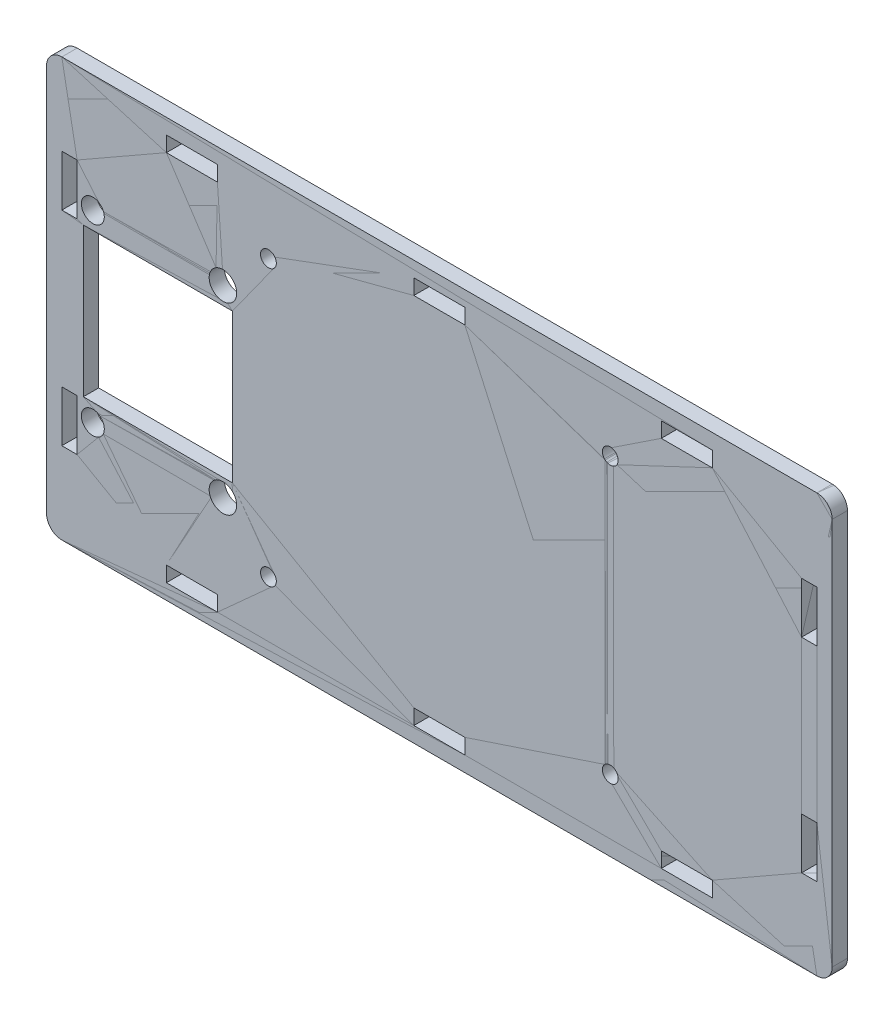
SolidWorks part; units mm, degrees
ref_plane "前视基准面" through (0, 0, 0) normal (0, 0, 1) x (1, 0, 0)
ref_plane "上视基准面" through (0, 0, 0) normal (0, 1, 0) x (1, 0, 0)
ref_plane "右视基准面" through (0, 0, 0) normal (1, 0, 0) x (0, 0, -1)
sketch "草图1" plane through (0, 0, 0) normal (0, 0, 1) x (1, 0, 0)
  line L0 (0, -9.5012) -> (46.4632, -9.5012) construction
  line L1 (-74, 31.4988) -> (74, 31.4988)
  line L2 (-77, 28.4988) -> (-77, -47.5012)
  line L3 (-74, -50.5012) -> (74, -50.5012)
  line L4 (77, 28.4988) -> (77, -47.5012)
  line L5 (-77, 31.4988) -> (77, -50.5012) construction
  line L6 (-77, -50.5012) -> (77, 31.4988) construction
  line L7 (-74, -24.5012) -> (-71, -24.5012)
  line L8 (-74, -24.5012) -> (-74, -34.5012)
  line L9 (-74, -34.5012) -> (-71, -34.5012)
  line L10 (-71, -24.5012) -> (-71, -34.5012)
  line L11 (-74, -24.5012) -> (-71, -34.5012) construction
  line L12 (-74, -34.5012) -> (-71, -24.5012) construction
  line L17 (-53.5, -44.5012) -> (-43.5, -44.5012)
  line L18 (-53.5, -44.5012) -> (-53.5, -47.5012)
  line L19 (-5, -44.5012) -> (5, -44.5012)
  line L20 (-5, -44.5012) -> (-5, -47.5012)
  line L21 (-5, -47.5012) -> (5, -47.5012)
  line L22 (5, -44.5012) -> (5, -47.5012)
  line L23 (-5, -44.5012) -> (5, -47.5012) construction
  line L24 (-5, -47.5012) -> (5, -44.5012) construction
  line L25 (-53.5, -47.5012) -> (-43.5, -47.5012)
  line L26 (-43.5, -44.5012) -> (-43.5, -47.5012)
  line L27 (-53.5, -44.5012) -> (-43.5, -47.5012) construction
  line L28 (-53.5, -47.5012) -> (-43.5, -44.5012) construction
  line L29 (0, -9.5012) -> (0, -75.1961) construction
  line L30 (-5, 28.4988) -> (5, 28.4988)
  line L31 (5, 25.4988) -> (5, 28.4988)
  line L32 (-5, 25.4988) -> (5, 25.4988)
  line L33 (-5, 25.4988) -> (-5, 28.4988)
  line L34 (-53.5, 28.4988) -> (-43.5, 28.4988)
  line L35 (-43.5, 25.4988) -> (-43.5, 28.4988)
  line L36 (-53.5, 25.4988) -> (-43.5, 25.4988)
  line L37 (-53.5, 25.4988) -> (-53.5, 28.4988)
  line L38 (-74, 15.4988) -> (-71, 15.4988)
  line L39 (-71, 5.4988) -> (-71, 15.4988)
  line L40 (-74, 5.4988) -> (-71, 5.4988)
  line L41 (-74, 5.4988) -> (-74, 15.4988)
  line L42 (53.5, -47.5012) -> (43.5, -47.5012)
  line L43 (43.5, -44.5012) -> (43.5, -47.5012)
  line L44 (53.5, -44.5012) -> (43.5, -44.5012)
  line L45 (53.5, -44.5012) -> (53.5, -47.5012)
  line L46 (74, -34.5012) -> (71, -34.5012)
  line L47 (71, -24.5012) -> (71, -34.5012)
  line L48 (74, -24.5012) -> (71, -24.5012)
  line L49 (74, -24.5012) -> (74, -34.5012)
  line L50 (74, 5.4988) -> (74, 15.4988)
  line L51 (74, 5.4988) -> (71, 5.4988)
  line L52 (71, 5.4988) -> (71, 15.4988)
  line L53 (74, 15.4988) -> (71, 15.4988)
  line L54 (53.5, 25.4988) -> (53.5, 28.4988)
  line L55 (53.5, 25.4988) -> (43.5, 25.4988)
  line L56 (43.5, 25.4988) -> (43.5, 28.4988)
  line L57 (53.5, 28.4988) -> (43.5, 28.4988)
  line L59 (-69.7799, 5.0788) -> (-40.5599, 5.0788)
  line L60 (-69.7799, 5.0788) -> (-69.7799, -24.0812)
  line L61 (-69.7799, -24.0812) -> (-40.5599, -24.0812)
  line L62 (-40.5599, 5.0788) -> (-40.5599, -24.0812)
  line L63 (-69.7799, 5.0788) -> (-40.5599, -24.0812) construction
  line L64 (-69.7799, -24.0812) -> (-40.5599, 5.0788) construction
  circle A0 centre (-33.5, 17.5) radius 1.55
  circle A1 centre (-33.5, -36.5025) radius 1.55
  circle A2 centre (33.5, -36.5025) radius 1.55
  circle A3 centre (33.5, 17.5) radius 1.55
  arc A5 (77, -47.5012) -> (74, -50.5012) centre (74, -47.5012) cw
  arc A6 (-74, -50.5012) -> (-77, -47.5012) centre (-74, -47.5012) cw
  arc A7 (74, 31.4988) -> (77, 28.4988) centre (74, 28.4988) cw
  arc A8 (-77, 28.4988) -> (-74, 31.4988) centre (-74, 28.4988) cw
  circle A9 centre (-42.4199, 8.4988) radius 2.7
  circle A10 centre (-67.9199, 8.4988) radius 2.2487
  circle A11 centre (-67.9199, -27.5012) radius 2.2487
  circle A12 centre (-42.4199, -27.5012) radius 2.7
  point P0 (0, -9.5012)
  point P5 (-72.5, -29.5012)
  point P10 (-43.7493, -32.7964)
  point P11 (-45.5, -46.0012)
  point P15 (0, -46.0012)
  point P34 (-48.5, -46.0012)
  point P61 (-55.1699, -9.5012)
  dimension "D9" = 3.1
  dimension "D10" = 3
  dimension "D13" = 3.42
  dimension "D1" = 154
  dimension "D2" = 82
  dimension "D3" = 3
  dimension "D4" = 10
  dimension "D5" = 3
  dimension "D6" = 16
  dimension "D7" = 3
  dimension "D8" = 23.5
  dimension "D11" = 29.22
  dimension "D12" = 29.16
  dimension "D14" = 1.86
  dimension "D15" = 25.5
extrude "凸台-拉伸3" add sketch "草图1<3>" along normal blind 3
sketch "草图1<3>" plane through (0, 0, 0) normal (0, 0, 1) x (1, 0, 0) same geometry as "草图1"
extrude "凸台-拉伸2" add sketch "草图1<2>" along normal blind 3
sketch "草图1<2>" plane through (0, 0, 0) normal (0, 0, 1) x (1, 0, 0) same geometry as "草图1"
extrude "凸台-拉伸1" add sketch "草图1" along normal blind 3
